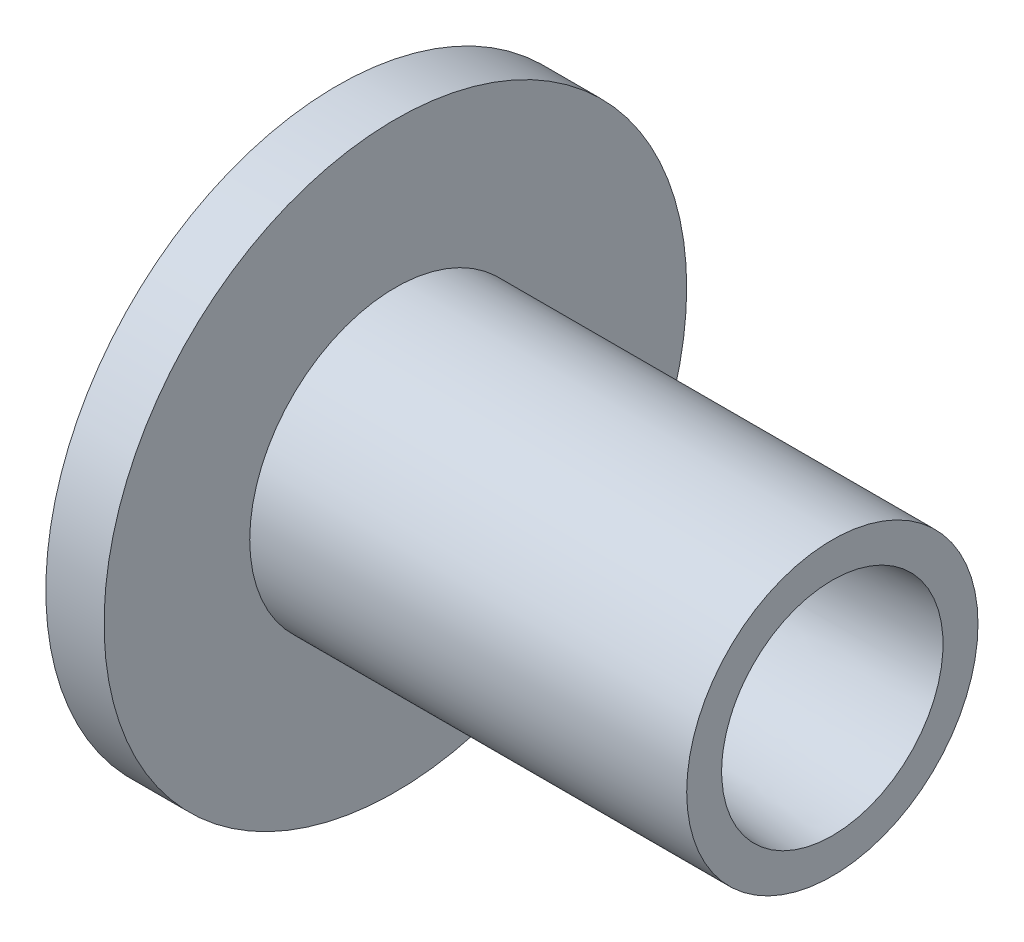
SolidWorks part; units mm, degrees
ref_plane "Front Plane" through (0, 0, 0) normal (0, 0, 1) x (1, 0, 0)
ref_plane "Top Plane" through (0, 0, 0) normal (0, 1, 0) x (1, 0, 0)
ref_plane "Right Plane" through (0, 0, 0) normal (1, 0, 0) x (0, 0, -1)
sketch "Sketch1" plane through (0, 0, 0) normal (1, 0, 0) x (0, 0, -1)
  circle A0 centre (0, 0) radius 12.7
  point P3 (0, 0)
extrude "Boss-Extrude1" add sketch "Sketch1" along normal blind 2.54
sketch "Sketch2" plane through (2.54, 0, 0) normal (1, 0, 0) x (0, 0, -1)
  circle A0 centre (0, 0) radius 6.35
extrude "Boss-Extrude2" add sketch "Sketch2" along normal blind 19.05
sketch "Sketch3" plane through (21.59, 0, 0) normal (1, 0, 0) x (0, 0, -1)
  circle A0 centre (0, 0) radius 4.826
sketch "Sketch4" plane through (0, 0, 0) normal (-1, 0, 0) x (0, 0, 1)
  circle A0 centre (0, 0) radius 3.175
loft "Cut-Loft1" cut profiles "Sketch4", "Sketch3" connector at (0, -0.0879, -3.1738) connector at (21.59, -1.3853, -4.6229)
